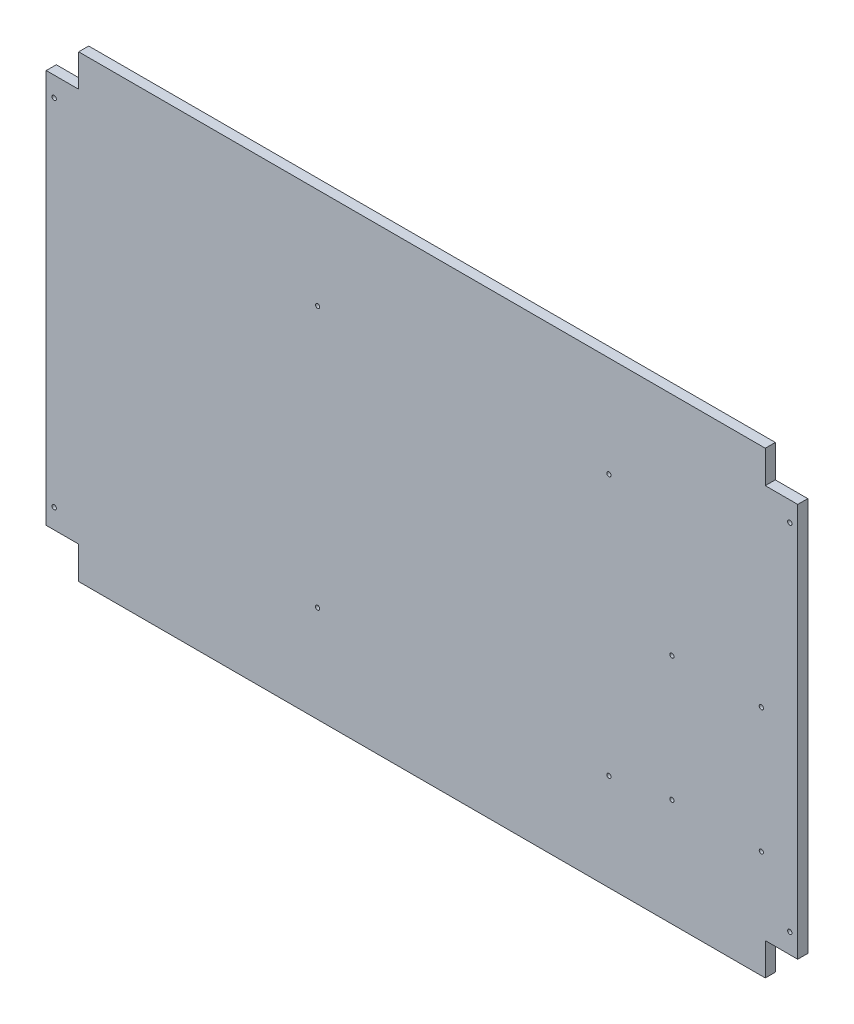
SolidWorks part; units mm, degrees
ref_plane "Front Plane" through (0, 0, 0) normal (0, 0, 1) x (1, 0, 0)
ref_plane "Top Plane" through (0, 0, 0) normal (0, 1, 0) x (1, 0, 0)
ref_plane "Right Plane" through (0, 0, 0) normal (1, 0, 0) x (0, 0, -1)
sketch "Sketch2" plane through (0, 0, 0) normal (0, 0, 1) x (1, 0, 0)
  line L1 (-475, -290) -> (475, -290)
  line L2 (-475, -290) -> (-475, 290)
  line L3 (-475, 290) -> (475, 290)
  line L4 (475, -290) -> (475, 290)
  line L5 (-475, -290) -> (475, 290) construction
  line L6 (-475, 290) -> (475, -290) construction
  point P0 (0, 0)
  dimension "D1" = 950
  dimension "D2" = 580
extrude "Boss-Extrude1" add sketch "Sketch2" along normal blind 12.7
sketch "Sketch3" plane through (0, 0, 12.7) normal (0, 0, 1) x (1, 0, 0)
  line L0 (0, 290) -> (0, -290) construction
  line L1 (-475, 290) -> (-434, 290)
  line L2 (-475, 290) -> (-475, 249)
  line L3 (-475, 249) -> (-434, 249)
  line L4 (-434, 290) -> (-434, 249)
  line L5 (-475, 290) -> (-434, 249) construction
  line L6 (-475, 249) -> (-434, 290) construction
  line L7 (475, 290) -> (-475, 290) construction
  line L8 (-475, -290) -> (475, -290) construction
  line L9 (-475, 0) -> (475, 0) construction
  line L10 (-475, 290) -> (-475, -290) construction
  line L11 (475, -290) -> (475, 290) construction
  line L12 (475, 249) -> (434, 290) construction
  line L13 (475, 290) -> (434, 249) construction
  line L14 (434, 290) -> (434, 249)
  line L15 (475, 249) -> (434, 249)
  line L16 (475, 290) -> (475, 249)
  line L17 (475, 290) -> (434, 290)
  line L18 (475, -290) -> (434, -249) construction
  line L19 (475, -249) -> (434, -290) construction
  line L20 (475, -290) -> (434, -290)
  line L21 (475, -290) -> (475, -249)
  line L22 (434, -290) -> (434, -249)
  line L23 (475, -249) -> (434, -249)
  line L24 (-475, -249) -> (-434, -290) construction
  line L25 (-475, -290) -> (-434, -249) construction
  line L26 (-434, -290) -> (-434, -249)
  line L27 (-475, -249) -> (-434, -249)
  line L28 (-475, -290) -> (-475, -249)
  line L29 (-475, -290) -> (-434, -290)
  point P4 (-454.5, 269.5)
  point P22 (454.5, 269.5)
  point P27 (454.5, -269.5)
  point P32 (-454.5, -269.5)
  dimension "D1" = 41
  dimension "D2" = 41
extrude "Cut-Extrude1" cut sketch "Sketch3" against normal up to next
sketch "Sketch4" plane through (0, 0, 12.7) normal (0, 0, 1) x (1, 0, 0)
  line L0 (-465, 249) -> (-465, -249) construction
  line L1 (-475, 249) -> (-434, 249) construction
  line L2 (-434, -249) -> (-475, -249) construction
  line L3 (0, 290) -> (0, -290) construction
  line L4 (434, 290) -> (-434, 290) construction
  line L5 (-434, -290) -> (434, -290) construction
  line L6 (0, 0) -> (-475, 0) construction
  line L7 (-475, 249) -> (-475, -249) construction
  circle A0 centre (-465, -224) radius 2.75
  circle A1 centre (-465, 224) radius 2.75
  circle A2 centre (465, -224) radius 2.75
  circle A3 centre (465, 224) radius 2.75
  dimension "D1" = 5.5
  dimension "D2" = 25
  dimension "D3" = 10
extrude "Cut-Extrude2" cut sketch "Sketch4" against normal up to next
sketch "Sketch6" plane through (0, 0, 12.7) normal (0, 0, 1) x (1, 0, 0)
  circle A0 centre (-131.9734, -167.5194) radius 2.665
  circle A1 centre (236.3266, -167.5194) radius 2.665
  circle A2 centre (236.3266, 162.6806) radius 2.665
  circle A3 centre (-131.9734, 162.6806) radius 2.665
  dimension "D1" = 5.33
extrude "Cut-Extrude3" cut sketch "Sketch6" against normal up to next
sketch "Sketch7" plane through (0, 0, 12.7) normal (0, 0, 1) x (1, 0, 0)
  circle A0 centre (429, 4) radius 2.665
  circle A1 centre (429, -154) radius 2.665
  circle A2 centre (316, 4) radius 2.665
  circle A3 centre (316, -154) radius 2.665
  dimension "D1" = 5.33
extrude "Cut-Extrude4" cut sketch "Sketch7" against normal up to next
